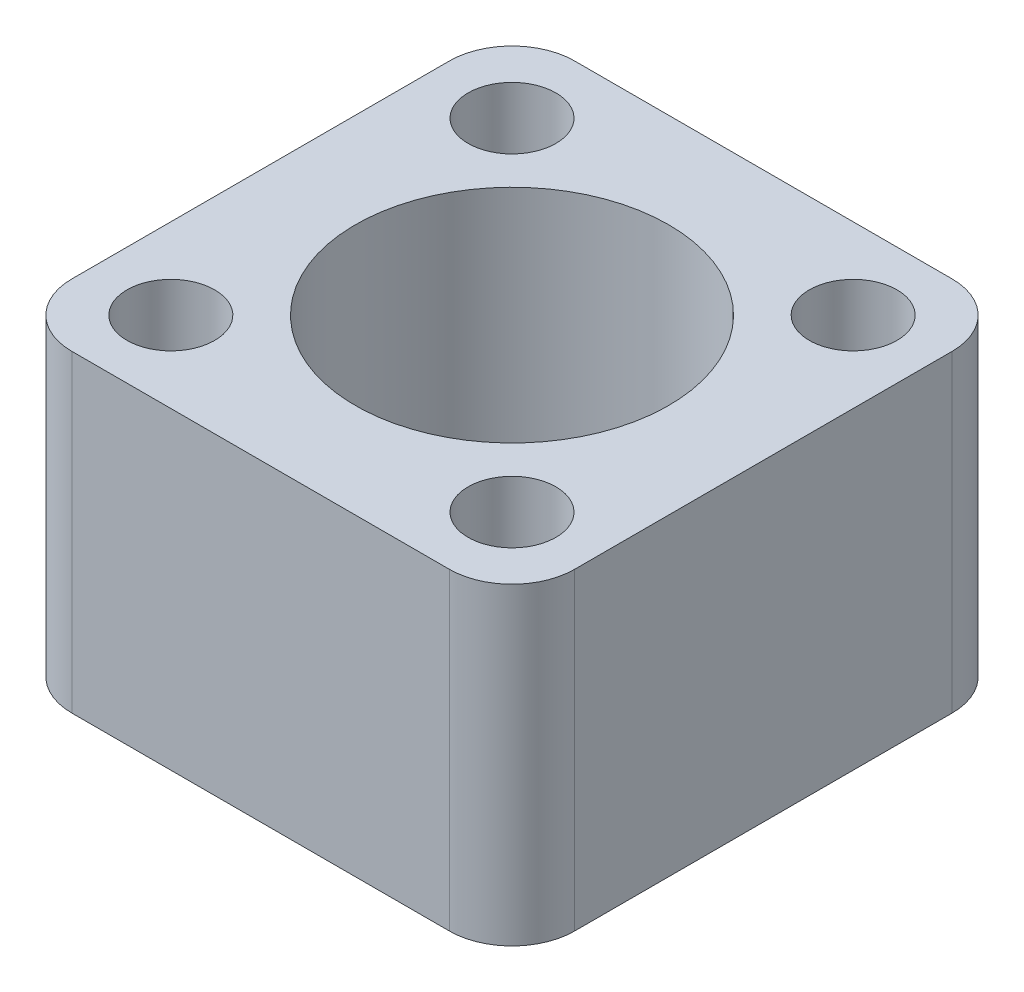
SolidWorks part; units mm, degrees
ref_plane "Front Plane" through (0, 0, 0) normal (0, 0, 1) x (1, 0, 0)
ref_plane "Top Plane" through (0, 0, 0) normal (0, 1, 0) x (1, 0, 0)
ref_plane "Right Plane" through (0, 0, 0) normal (1, 0, 0) x (0, 0, -1)
sketch "Sketch3" plane through (0, 0, 0) normal (0, 1, 0) x (1, 0, 0)
  line L1 (0, 0) -> (-20.3852, 0)
  line L2 (0, 0) -> (0, 20.3852)
  line L3 (0, 20.3852) -> (-20.3852, 20.3852)
  line L4 (-20.3852, 0) -> (-20.3852, 20.3852)
  dimension "D1" = 28.829
extrude "Boss-Extrude2" add sketch "Sketch3" along normal blind 12.7 contours L3 L4 L1 L2
sketch "Sketch8" plane through (0, 0, 0) normal (0, -1, 0) x (1, 0, 0)
  line L0 (0, -20.3852) -> (-10.1926, -10.1926) construction
  line L1 (-10.1926, -10.1926) -> (-17.1074, -17.1074) construction
  line L2 (-10.1926, -10.1926) -> (-3.2778, -17.1074) construction
  line L3 (-10.1926, -10.1926) -> (-3.2778, -3.2778) construction
  line L4 (-10.1926, -10.1926) -> (-17.1074, -3.2778) construction
  circle A0 centre (-3.2778, -17.1074) radius 1.778
  circle A1 centre (-17.1074, -17.1074) radius 1.778
  circle A2 centre (-17.1074, -3.2778) radius 1.778
  circle A3 centre (-3.2778, -3.2778) radius 1.778
  circle A4 centre (-10.1926, -10.1926) radius 6.35
extrude "Cut-Extrude4" cut sketch "Sketch8" against normal blind 12.7
fillet "Fillet2" radius 2.54 4 edges at (-20.3852, 6.35, 0) (0, 6.35, 0) (0, 6.35, -20.3852) (-20.3852, 6.35, -20.3852)
